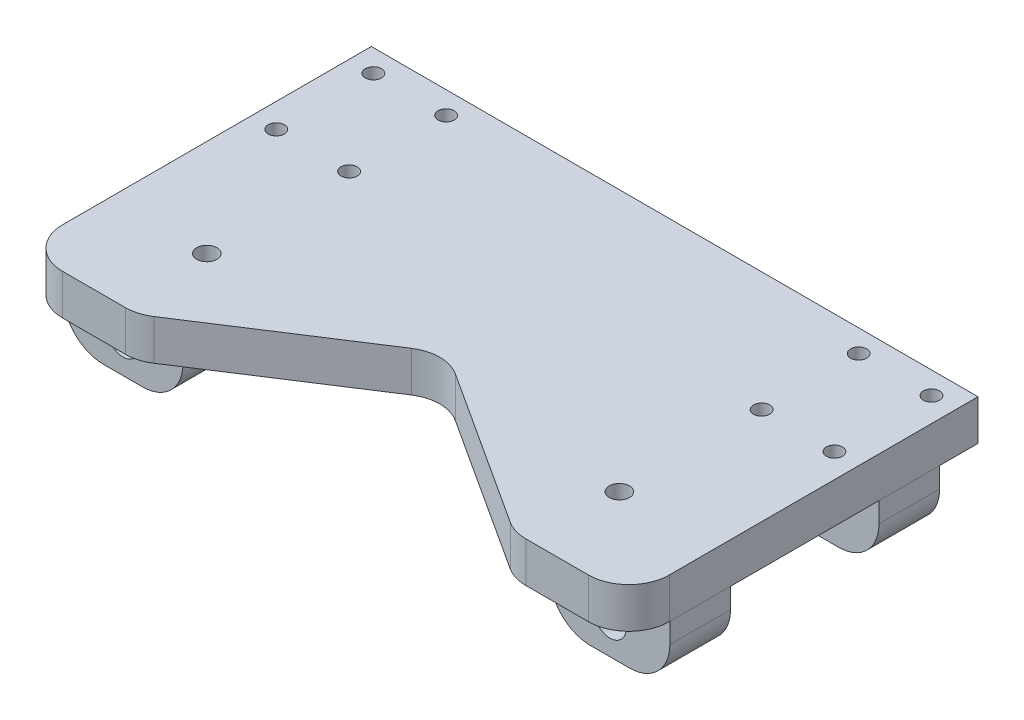
SolidWorks part; units mm, degrees
material "Plywood"
ref_plane "Front Plane" through (0, 0, 0) normal (0, 0, 1) x (1, 0, 0)
ref_plane "Top Plane" through (0, 0, 0) normal (0, 1, 0) x (1, 0, 0)
ref_plane "Right Plane" through (0, 0, 0) normal (1, 0, 0) x (0, 0, -1)
sketch "Sketch3" plane through (0, 0, 0) normal (0, 1, 0) x (1, 0, 0)
  line L0 (75.4469, -0.5285) -> (-74.5531, -0.5285) construction
  line L2 (-74.5531, -18.0285) -> (-74.5531, 16.9715)
  line L3 (-74.5531, 16.9715) -> (75.4469, 16.9715)
  line L4 (75.4469, -18.0285) -> (75.4469, 16.9715)
  line L5 (0.4469, -39.1916) -> (0.4469, 16.9715) construction
  line L7 (-68.5531, 11.4715) -> (-50.5531, 11.4715) construction
  line L8 (-68.5531, 11.4715) -> (-68.5531, -12.5285) construction
  line L9 (-68.5531, -12.5285) -> (-50.5531, -12.5285) construction
  line L10 (-50.5531, 11.4715) -> (-50.5531, -12.5285) construction
  line L11 (-68.5531, 11.4715) -> (-50.5531, -12.5285) construction
  line L12 (-68.5531, -12.5285) -> (-50.5531, 11.4715) construction
  line L19 (-74.5531, -18.0285) -> (-74.5531, -59.3519)
  line L20 (-64.5531, -69.3519) -> (-49.0669, -69.3519)
  line L23 (-43.63, -67.7448) -> (-4.99, -42.7137)
  line L24 (75.4469, -18.0285) -> (75.4469, -59.3519)
  line L25 (65.4469, -69.3519) -> (49.9607, -69.3519)
  line L26 (44.5238, -67.7448) -> (5.8838, -42.7137)
  circle A0 centre (-68.5531, 11.4715) radius 2
  circle A1 centre (-50.5531, 11.4715) radius 2
  circle A2 centre (-68.5531, -12.5285) radius 2
  circle A3 centre (-50.5531, -12.5285) radius 2
  circle A4 centre (51.4469, -12.5285) radius 2
  circle A5 centre (69.4469, -12.5285) radius 2
  circle A6 centre (69.4469, 11.4715) radius 2
  circle A7 centre (51.4469, 11.4715) radius 2
  arc A8 (75.4469, -59.3519) -> (65.4469, -69.3519) centre (65.4469, -59.3519) cw
  arc A9 (49.9607, -69.3519) -> (44.5238, -67.7448) centre (49.9607, -59.3519) cw
  arc A10 (-74.5531, -59.3519) -> (-64.5531, -69.3519) centre (-64.5531, -59.3519) ccw
  arc A11 (-49.0669, -69.3519) -> (-43.63, -67.7448) centre (-49.0669, -59.3519) ccw
  arc A12 (5.8838, -42.7137) -> (-4.99, -42.7137) centre (0.4469, -51.1065) ccw
  circle A13 centre (-50.5531, -47.6933) radius 2.5
  circle A14 centre (51.4469, -47.6933) radius 2.5
  point P0 (0, 0)
  point P6 (-59.5531, -0.5285)
  point P33 (75.4469, -69.3519)
  point P36 (47.0047, -69.3519)
  point P39 (-74.5531, -69.3519)
  point P42 (-46.1109, -69.3519)
  dimension "D5" = 15
  dimension "D6" = 10
  dimension "D1" = 150
  dimension "D2" = 35
  dimension "D3" = 24
  dimension "D4" = 18
extrude "Boss-Extrude3" add sketch "Sketch3" along normal blind 10
sketch "Sketch4" plane through (0, 0, 0) normal (0, -1, 0) x (1, 0, 0)
  line L0 (-74.5531, 25.8566) -> (75.4469, 25.8566) construction
  line L1 (-74.5531, -7.5) -> (-44.9311, -7.5)
  line L2 (-74.5531, -7.5) -> (-74.5531, 7.5)
  line L3 (-74.5531, 7.5) -> (-44.9311, 7.5)
  line L4 (-44.9311, -7.5) -> (-44.9311, 7.5)
  line L5 (-74.5531, -7.5) -> (-44.9311, 7.5) construction
  line L6 (-74.5531, 7.5) -> (-44.9311, -7.5) construction
  line L7 (-74.5531, -16.9715) -> (-74.5531, 59.3519) construction
  line L8 (75.4469, -16.9715) -> (-74.5531, -16.9715) construction
  line L9 (-74.5531, -16.9715) -> (-74.5531, 59.3519) construction
  line L10 (-74.5531, 0) -> (75.4469, 0) construction
  line L11 (75.4469, 59.3519) -> (75.4469, -16.9715) construction
  line L12 (75.439, 7.5) -> (45.8091, 7.5)
  line L13 (45.8091, -7.5) -> (45.8091, 7.5)
  line L14 (75.439, -7.5) -> (45.8091, -7.5)
  line L15 (75.439, -7.5) -> (75.439, 7.5)
  line L16 (0.439, -16.9715) -> (0.439, 47.9553) construction
  line L17 (75.4469, 59.3519) -> (75.4469, -16.9715) construction
  line L18 (75.439, 59.2132) -> (75.439, 44.2132)
  line L19 (75.439, 59.2132) -> (45.8091, 59.2132)
  line L20 (45.8091, 59.2132) -> (45.8091, 44.2132)
  line L21 (75.439, 44.2132) -> (45.8091, 44.2132)
  line L22 (-74.5531, 44.2132) -> (-44.9311, 44.2132)
  line L23 (-44.9311, 59.2132) -> (-44.9311, 44.2132)
  line L24 (-74.5531, 59.2132) -> (-44.9311, 59.2132)
  line L25 (-74.5531, 59.2132) -> (-74.5531, 44.2132)
  point P0 (-59.7421, 0)
  dimension "D1" = 15
extrude "Boss-Extrude4" add sketch "Sketch4" along normal blind 15
fillet "Fillet1" radius 10 4 edges at (75.439, -15, 0) (45.8091, -15, 0) (-44.9311, -15, 0) (-74.5531, -15, 0)
sketch "Sketch5" plane through (0, 0, 7.5) normal (0, 0, 1) x (1, 0, 0)
  line L0 (-74.5531, -7.004) -> (-44.9311, -7.004) construction
  line L1 (-74.5531, -5) -> (-74.5531, 0) construction
  line L2 (-44.9311, -5) -> (-44.9311, 0) construction
  line L3 (0.439, 10) -> (0.439, -16.9448) construction
  circle A0 centre (-59.7421, -7.004) radius 4
  circle A1 centre (60.6201, -7.004) radius 4
extrude "Cut-Extrude1" cut sketch "Sketch5" against normal blind 15 and the other way blind 57
fillet "Fillet3" radius 10 4 edges at (75.439, -15, 51.7132) (45.8091, -15, 51.7132) (-44.9311, -15, 51.7132) (-74.5531, -15, 51.7132)
sketch "Sketch7" plane through (0, 10, 0) normal (0, 1, 0) x (1, 0, 0)
  line L0 (-50.5531, -47.6933) -> (-26.0996, -31.8523) construction
  line L1 (-50.5531, -47.6933) -> (-66.463, -31.7834) construction
  line L2 (-50.5531, -47.6933) -> (-66.3034, -63.4436) construction
  line L3 (-43.63, -67.7448) -> (-4.99, -42.7137) construction
  circle A0 centre (-66.463, -31.7834) radius 2.25
  circle A1 centre (-26.0996, -31.8523) radius 2.25
  circle A2 centre (-66.3034, -63.4436) radius 2.25
